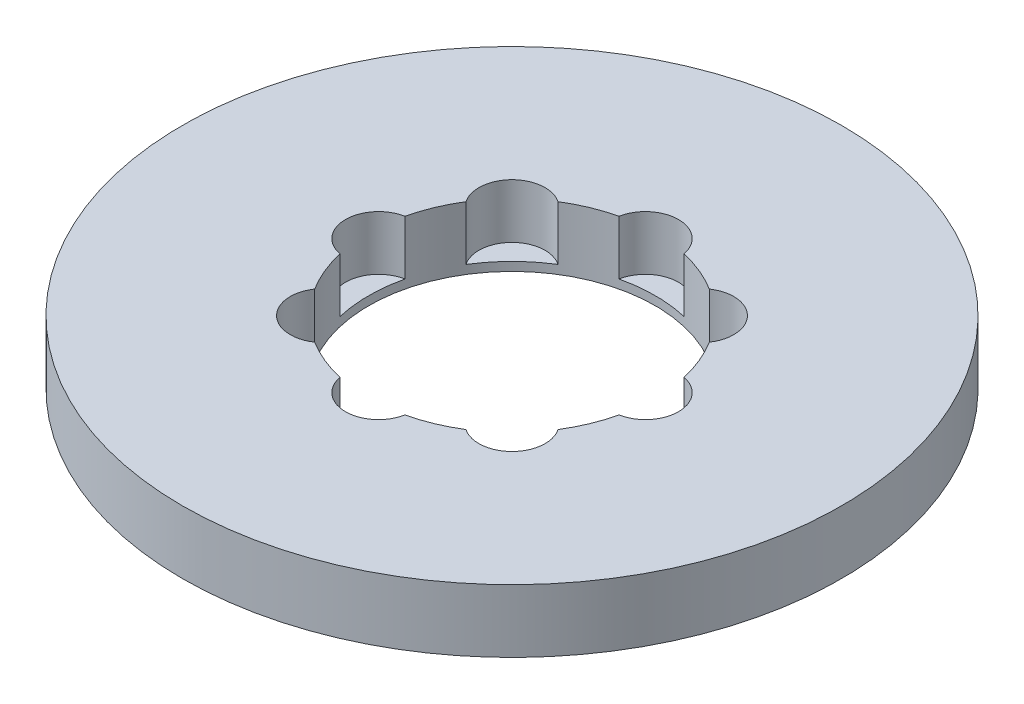
SolidWorks part; units mm, degrees
ref_plane "Front Plane" through (0, 0, 0) normal (0, 0, 1) x (1, 0, 0)
ref_plane "Top Plane" through (0, 0, 0) normal (0, 1, 0) x (1, 0, 0)
ref_plane "Right Plane" through (0, 0, 0) normal (1, 0, 0) x (0, 0, -1)
sketch "Sketch1" plane through (0, 0, 0) normal (0, 1, 0) x (1, 0, 0)
  circle A0 centre (0, 0) radius 57.5
  dimension "FLANGE_OD" = 115
extrude "Boss-Extrude1" add sketch "Sketch1" along normal blind 11
sketch "Sketch2" plane through (0, 0, 0) normal (0, 1, 0) x (1, 0, 0)
  circle A0 centre (0, 0) radius 25
  dimension "BORE_D" = 50
extrude "Cut-Extrude1" cut sketch "Sketch2" along normal through all
sketch "Sketch3" plane through (0, 11, 0) normal (0, 1, 0) x (1, 0, 0)
  circle A0 centre (0, 0) radius 23.2715 construction
  circle A1 centre (-23.2715, 0) radius 5.7769
  dimension "BOLT_D" = 11.5538
  dimension "BOLT_PCD" = 46.5429
extrude "Cut-Extrude2" cut sketch "Sketch3" against normal blind 9.4807
pattern_circular "CirPattern1" count 8 over 360 about axis through (0, 0, 0) along (0, 1, 0) of "Cut-Extrude2"
